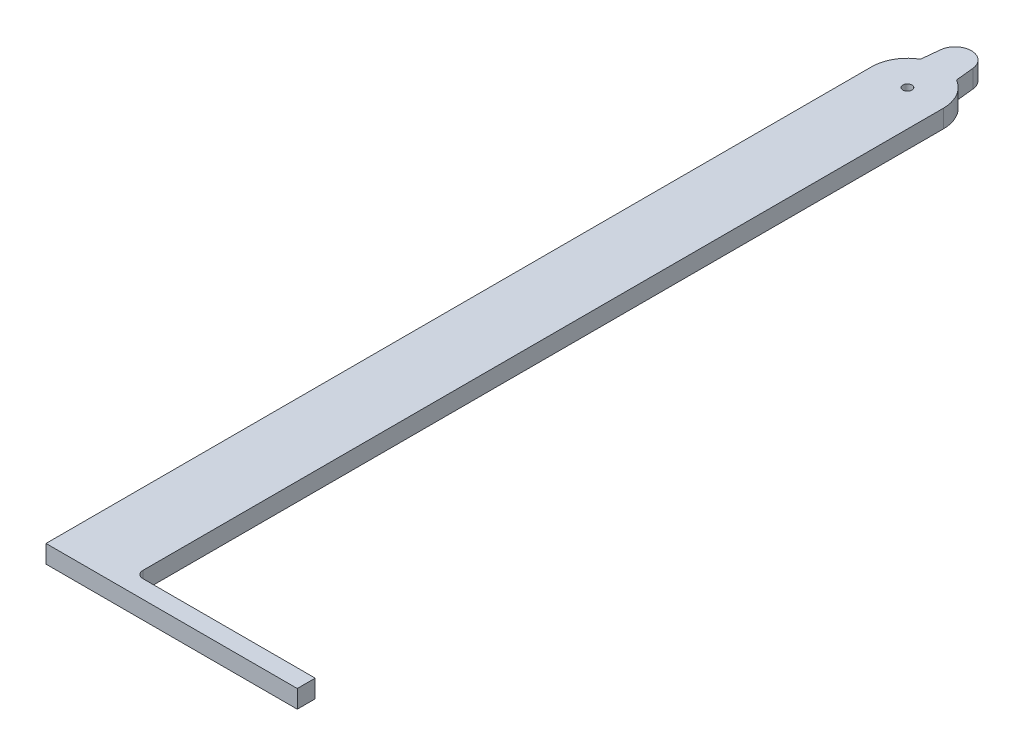
SolidWorks part; units mm, degrees
ref_plane "Front Plane" through (0, 0, 0) normal (0, 0, 1) x (1, 0, 0)
ref_plane "Top Plane" through (0, 0, 0) normal (0, 1, 0) x (1, 0, 0)
ref_plane "Right Plane" through (0, 0, 0) normal (1, 0, 0) x (0, 0, -1)
sketch "Sketch1" plane through (0, 0, 0) normal (0, 1, 0) x (1, 0, 0)
  line L1 (-12.7, 0) -> (12.7, 0)
  line L2 (-12.7, 0) -> (-12.7, -285.75)
  line L3 (-12.7, -285.75) -> (12.7, -285.75)
  line L4 (12.7, 0) -> (12.7, -285.75)
  circle A0 centre (0, 0) radius 12.7
  dimension "D1" = 25.4
  dimension "D2" = 285.75
extrude "Boss-Extrude1" add sketch "Sketch1" along normal blind 6.35 contours A0 L2 L3 L4 | L1 A0 | L1 A0 region at (0, 0, -5.39) region at (0, 0, 147.8477) region at (0, 0, 5.39)
sketch "Sketch2" plane through (0, 6.35, 0) normal (0, 1, 0) x (1, 0, 0)
  line L1 (-12.7, -285.75) -> (76.2, -285.75)
  line L2 (-12.7, -285.75) -> (-12.7, -292.1)
  line L3 (-12.7, -292.1) -> (76.2, -292.1)
  line L4 (76.2, -285.75) -> (76.2, -292.1)
  dimension "D1" = 88.9
  dimension "D2" = 6.35
extrude "Boss-Extrude2" add sketch "Sketch2" against normal up to surface (6.35 mm away) up to face at (0, 0, 139.7)
fillet "Fillet1" radius 2.54 1 edges
sketch "Sketch3" plane through (0, 0, 0) normal (0, -1, 0) x (-1, 0, 0)
  line L4 (-7.3841, 1.2138) -> (7.3841, 1.2138)
  line L6 (-7.3841, 1.2138) -> (-5.6981, 17.4684)
  line L7 (5.6981, 17.4684) -> (7.3841, 1.2138)
  line L8 (-7.3841, 1.2138) -> (-5.6981, 17.4684)
  line L9 (5.6981, 17.4684) -> (7.3841, 1.2138)
  arc A3 (5.6981, 17.4684) -> (-5.6981, 17.4684) centre (0, 16.8774) ccw
  arc A4 (5.6981, 17.4684) -> (-5.6981, 17.4684) centre (0, 16.8774) ccw
  dimension "D1" = 3.175
extrude "Boss-Extrude3" add sketch "Sketch3" against normal up to surface (6.35 mm away) up to face at (28.2277, 6.35, 183.5902)
sketch "Sketch4" plane through (0, 0, 0) normal (0, -1, 0) x (-1, 0, 0)
  circle A0 centre (0, 0) radius 1.5875
  dimension "D1" = 3.175
extrude "Cut-Extrude1" cut sketch "Sketch4" against normal through all
